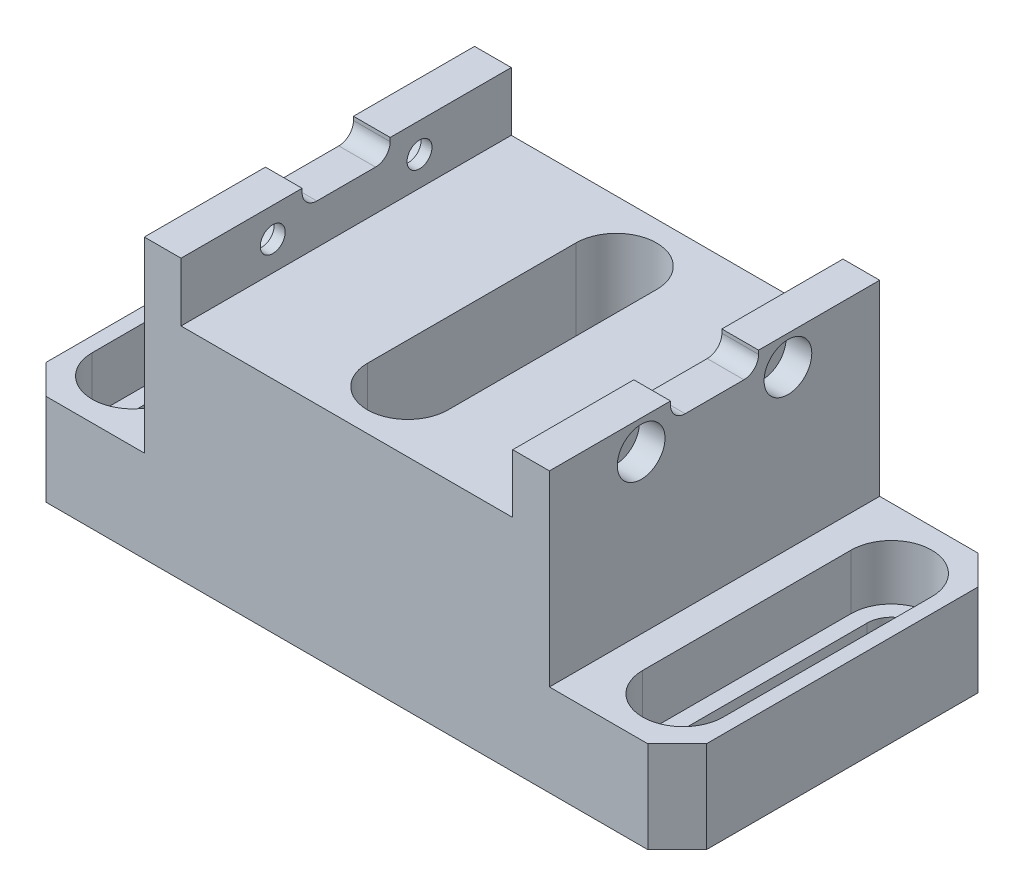
SolidWorks part; units mm, degrees
ref_plane "Front" through (0, 0, 0) normal (0, 0, 1) x (1, 0, 0)
ref_plane "Top" through (0, 0, 0) normal (0, 1, 0) x (1, 0, 0)
ref_plane "Right" through (0, 0, 0) normal (1, 0, 0) x (0, 0, -1)
sketch "Sketch1" plane through (0, 0, 0) normal (0, 1, 0) x (1, 0, 0)
  line L5 (-45, 22.5) -> (45, 22.5)
  line L6 (-45, 22.5) -> (-45, -22.5)
  line L7 (-45, -22.5) -> (45, -22.5)
  line L8 (45, 22.5) -> (45, -22.5)
  point P4 (0, 22.5)
  point P7 (-45, 0)
  dimension "D1" = 45
  dimension "D6" = 90
extrude "Boss-Extrude1" add sketch "Sketch1" along normal blind 30
sketch "Sketch2" plane through (0, 30, 0) normal (0, 1, 0) x (1, 0, 0)
  line L0 (45, 22.5) -> (-45, 22.5) construction
  line L1 (-27.6, 22.5) -> (-22.6, 22.5)
  line L2 (-27.6, 22.5) -> (-27.6, -22.5)
  line L3 (-27.6, -22.5) -> (-22.6, -22.5)
  line L4 (-22.6, 22.5) -> (-22.6, -22.5)
  line L5 (-45, -22.5) -> (45, -22.5) construction
  line L6 (-22.6, 0) -> (22.6, 0) construction
  line L7 (22.6, -22.5) -> (27.6, -22.5)
  line L8 (22.6, -22.5) -> (22.6, 22.5)
  line L9 (22.6, 22.5) -> (27.6, 22.5)
  line L10 (27.6, -22.5) -> (27.6, 22.5)
  dimension "D1" = 45.2
  dimension "D2" = 5
extrude "Boss-Extrude2" add sketch "Sketch2" along normal blind 8
hole_wizard "CBORE SLOT for M6 Hex Socket Head Cap Screw1" positions "Sketch3" profile "Sketch4" size "M6" standard "DIN" slot yes end condition through all
sketch "Sketch3" plane through (0, 30, 0) normal (0, 1, 0) x (1, 0, 0)
  line L0 (-37.5, 17.5) -> (-37.5, -17.5) construction
  point P0 (-37.5, 0)
  point P4 (37.5, 0)
  point P13 (0, 0)
  dimension "D1" = 35
  dimension "D2" = 37.5
  dimension "D3" = 37.5
sketch "Sketch4" plane through (-37.5, 30, 0) normal (1, 0, 0) x (0, 0, 1)
  line L0 (0, 0) -> (0, 30)
  line L1 (0, 30) -> (3.3, 30)
  line L3 (3.3, 30) -> (3.3, 25)
  line L4 (3.3, 25) -> (5.5, 25)
  line L5 (5.5, 25) -> (5.5, 0)
  line L7 (5.5, 0) -> (0, 0)
  line L11 (0, -6.35) -> (0, 107.95) construction
  dimension "Thru Hole Dia." = 6.6
  dimension "Thru Hole Depth" = 30
  dimension "C'Bore Dia." = 11
  dimension "C'Bore Depth" = 25
chamfer "Chamfer2" distance 4 angle 45 4 edges at (45, 15, -22.5) (45, 15, 22.5) (-45, 15, 22.5) (-45, 15, -22.5)
hole_wizard "CBORE for M3 Hex Socket Head Cap Screw1" positions "Sketch7" profile "Sketch8" counterbore size "M3" standard "DIN" end condition up to next
sketch "Sketch7" plane through (27.6, 0, 0) normal (1, 0, 0) x (0, 0, -1)
  line L0 (-22.5, 30) -> (22.5, 30) construction
  point P0 (-10, 34)
  point P2 (10, 34)
  dimension "D1" = 4
  dimension "D2" = 20
  dimension "D3" = 10
sketch "Sketch8" plane through (27.6, 34, 10) normal (0, 1, 0) x (0, 0, -1)
  line L0 (0, 0) -> (0, 5)
  line L1 (0, 5) -> (1.7, 5)
  line L3 (1.7, 5) -> (1.7, 3.5)
  line L4 (1.7, 3.5) -> (3.25, 3.5)
  line L5 (3.25, 3.5) -> (3.25, 0)
  line L7 (3.25, 0) -> (0, 0)
  line L11 (0, -6.35) -> (0, 107.95) construction
  dimension "Thru Hole Dia." = 3.4
  dimension "Thru Hole Depth" = 5
  dimension "C'Bore Dia." = 6.5
  dimension "C'Bore Depth" = 3.5
hole_wizard "CBORE for M3 Hex Socket Head Cap Screw2" positions "Sketch9" profile "Sketch10" counterbore size "M3" standard "DIN" end condition up to next
sketch "Sketch9" plane through (-27.6, 0, 0) normal (-1, 0, 0) x (0, 0, 1)
  circle A0 centre (-10, 34) radius 1.7 construction
  circle A1 centre (10, 34) radius 1.7 construction
  point P0 (-10, 34)
  point P2 (10, 34)
sketch "Sketch10" plane through (-27.6, 34, -10) normal (0, 1, 0) x (0, 0, 1)
  line L0 (0, 0) -> (0, 5)
  line L1 (0, 5) -> (1.7, 5)
  line L3 (1.7, 5) -> (1.7, 3.5)
  line L4 (1.7, 3.5) -> (3.25, 3.5)
  line L5 (3.25, 3.5) -> (3.25, 0)
  line L7 (3.25, 0) -> (0, 0)
  line L11 (0, -6.35) -> (0, 107.95) construction
  dimension "Thru Hole Dia." = 3.4
  dimension "Thru Hole Depth" = 5
  dimension "C'Bore Dia." = 6.5
  dimension "C'Bore Depth" = 3.5
sketch "Sketch11" plane through (27.6, 0, 0) normal (1, 0, 0) x (0, 0, -1)
  line L0 (-22.5, 38) -> (22.5, 38) construction
  line L1 (-6, 38) -> (6, 38)
  line L2 (-6, 38) -> (-6, 35.5)
  line L3 (-6, 35.5) -> (6, 35.5)
  line L4 (6, 38) -> (6, 35.5)
  point P7 (0, 38)
  dimension "D1" = 12
  dimension "D2" = 2.5
extrude "Cut-Extrude1" cut sketch "Sketch11" against normal up to surface (55.2 mm away) up to face at (-27.6, 34, 0)
fillet "Fillet1" radius 2 4 edges at (-25.1, 35.5, 6) (-25.1, 35.5, -6) (25.1, 35.5, 6) (25.1, 35.5, -6)
sketch "Sketch13" plane through (0, 30, 0) normal (0, 1, 0) x (1, 0, 0)
  line L6 (-45, 18.5) -> (-45, -18.5)
  line L7 (-45, -18.5) -> (-41, -22.5)
  line L8 (-41, -22.5) -> (-27.6, -22.5)
  line L9 (-27.6, -22.5) -> (-27.6, 22.5)
  line L10 (-27.6, 22.5) -> (-41, 22.5)
  line L11 (-41, 22.5) -> (-45, 18.5)
  line L12 (-45, 18.5) -> (-45, -18.5)
  line L13 (-45, -18.5) -> (-41, -22.5)
  line L14 (-41, -22.5) -> (-27.6, -22.5)
  line L15 (-27.6, -22.5) -> (-27.6, 22.5)
  line L16 (-27.6, 22.5) -> (-41, 22.5)
  line L17 (-41, 22.5) -> (-45, 18.5)
  line L24 (45, -18.5) -> (45, 18.5)
  line L25 (45, 18.5) -> (41, 22.5)
  line L26 (41, 22.5) -> (27.6, 22.5)
  line L27 (27.6, 22.5) -> (27.6, -22.5)
  line L28 (27.6, -22.5) -> (41, -22.5)
  line L29 (41, -22.5) -> (45, -18.5)
  line L30 (45, -18.5) -> (45, 18.5)
  line L31 (45, 18.5) -> (41, 22.5)
  line L32 (41, 22.5) -> (27.6, 22.5)
  line L33 (27.6, 22.5) -> (27.6, -22.5)
  line L34 (27.6, -22.5) -> (41, -22.5)
  line L35 (41, -22.5) -> (45, -18.5)
  dimension "D1" = 0
  dimension "D2" = 0
extrude "Cut-Extrude3" cut sketch "Sketch13" against normal blind 17.5
